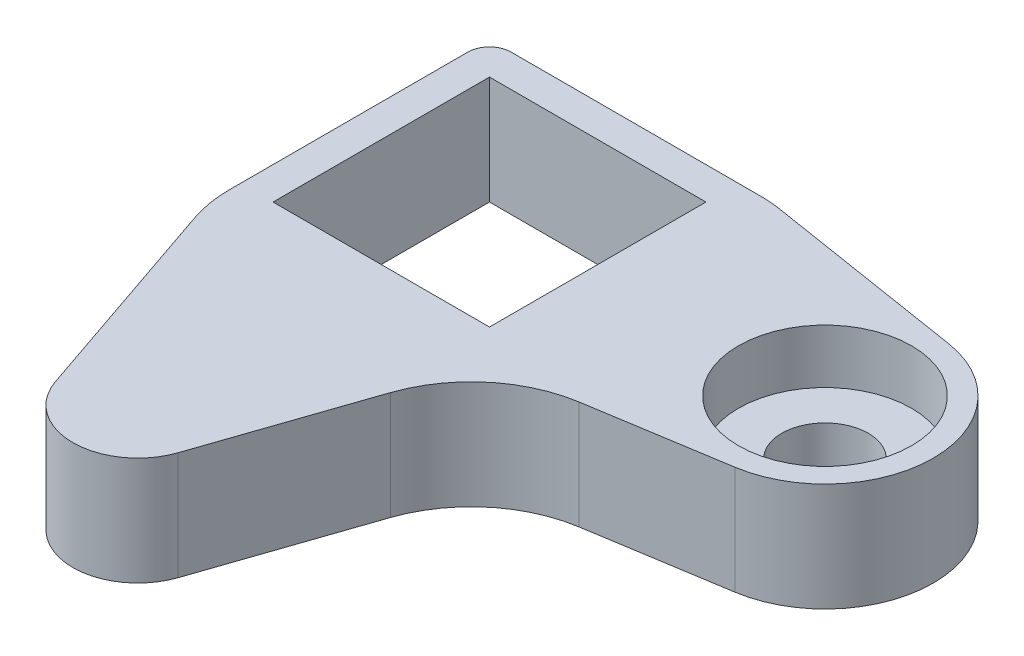
SolidWorks part; units mm, degrees
ref_plane "Front Plane" through (0, 0, 0) normal (0, 0, 1) x (1, 0, 0)
ref_plane "Top Plane" through (0, 0, 0) normal (0, 1, 0) x (1, 0, 0)
ref_plane "Right Plane" through (0, 0, 0) normal (1, 0, 0) x (0, 0, -1)
sketch "Sketch1" plane through (0, 0, 0) normal (0, 1, 0) x (1, 0, 0)
  line L0 (20, 0) -> (41, -10) construction
  line L1 (10, -42.5) -> (0, -20) construction
  line L2 (41, -10) -> (20, -20) construction
  line L3 (0, 0) -> (0, -20) construction
  line L4 (0, 0) -> (20, -20) construction
  line L5 (23.9399, 2.85) -> (42.5764, -0.125)
  line L12 (-3, -23) -> (23, -23) construction
  line L13 (0, 0) -> (20, 0) construction
  line L14 (0, 0) -> (0, -20) construction
  line L15 (0, -20) -> (20, -20) construction
  line L16 (20, 0) -> (20, -20) construction
  line L17 (10, -42.5) -> (20, -20) construction
  line L18 (-3, -21.0074) -> (-3, 1)
  line L19 (-1, 3) -> (22.0482, 3)
  line L20 (23, -23) -> (23, 3) construction
  line L21 (-3, -23) -> (23, 3) construction
  line L22 (-3, 3) -> (23, -23) construction
  line L23 (0, -20) -> (20, -20)
  line L24 (0, -20) -> (0, 0)
  line L25 (0, 0) -> (20, 0)
  line L26 (20, -20) -> (20, 0)
  line L27 (0, -20) -> (20, 0) construction
  line L28 (0, 0) -> (20, -20) construction
  line L29 (30.1306, -21.8617) -> (42.5764, -19.875)
  line L30 (20.6662, -29.8333) -> (15.678, -44.4392)
  line L31 (-2.356, -24.8857) -> (4.322, -44.4392)
  circle A4 centre (10, -42.5) radius 4 construction
  circle A5 centre (41, -10) radius 4 construction
  arc A6 (-3, 1) -> (-1, 3) centre (-1, 1) cw
  circle A7 centre (41, -10) radius 8 construction
  arc A8 (42.5764, -19.875) -> (42.5764, -0.125) centre (41, -10) ccw
  arc A9 (4.322, -44.4392) -> (15.678, -44.4392) centre (10, -42.5) ccw
  arc A10 (30.1306, -21.8617) -> (20.6662, -29.8333) centre (32.0222, -33.7117) ccw
  arc A11 (23.9399, 2.85) -> (22.0482, 3) centre (22.0482, -9) ccw
  arc A12 (-3, -21.0074) -> (-2.356, -24.8857) centre (9, -21.0074) ccw
  point P0 (10, -10)
  point P10 (10, -10)
  dimension "D6" = 8
  dimension "D7" = 16
  dimension "D8" = 20
  dimension "D9" = 12
  dimension "D10" = 12
  dimension "D11" = 12
  dimension "D5" = 2
  dimension "D2" = 20
  dimension "D3" = 3
  dimension "D4" = 42.5
  dimension "D12" = 20
  dimension "D13" = 41
extrude "Boss-Extrude1" add sketch "Sketch1" along normal blind 10
ref_plane "Plane1" through (0, 5, 0) normal (0, 1, 0) x (1, 0, 0)
sketch "Sketch2" plane through (0, 5, 0) normal (0, 1, 0) x (1, 0, 0)
  line L0 (20, 0) -> (41, -10) construction
  line L1 (10, -42.5) -> (0, -20) construction
  line L2 (41, -10) -> (20, -20) construction
  line L3 (0, 0) -> (0, -20) construction
  line L4 (0, 0) -> (20, -20) construction
  line L5 (23.9399, 2.85) -> (42.5764, -0.125) construction
  line L6 (-3, -23) -> (23, -23) construction
  line L7 (0, 0) -> (20, 0) construction
  line L8 (0, 0) -> (0, -20) construction
  line L9 (0, -20) -> (20, -20) construction
  line L10 (20, 0) -> (20, -20) construction
  line L11 (10, -42.5) -> (20, -20) construction
  line L12 (-3, -21.0074) -> (-3, 1) construction
  line L13 (-1, 3) -> (22.0482, 3) construction
  line L14 (23, -23) -> (23, 3) construction
  line L15 (-3, -23) -> (23, 3) construction
  line L16 (-3, 3) -> (23, -23) construction
  line L17 (0, -20) -> (20, -20) construction
  line L18 (0, -20) -> (0, 0) construction
  line L19 (0, 0) -> (20, 0) construction
  line L20 (20, -20) -> (20, 0) construction
  line L21 (0, -20) -> (20, 0) construction
  line L22 (0, 0) -> (20, -20) construction
  line L23 (30.1306, -21.8617) -> (42.5764, -19.875) construction
  line L24 (20.6662, -29.8333) -> (15.678, -44.4392) construction
  line L25 (-2.356, -24.8857) -> (4.322, -44.4392) construction
  circle A0 centre (10, -42.5) radius 4 construction
  circle A1 centre (41, -10) radius 4 construction
  arc A2 (-3, 1) -> (-1, 3) centre (-1, 1) cw construction
  circle A3 centre (41, -10) radius 8
  arc A4 (42.5764, -19.875) -> (42.5764, -0.125) centre (41, -10) ccw construction
  arc A5 (4.322, -44.4392) -> (15.678, -44.4392) centre (10, -42.5) ccw construction
  arc A6 (30.1306, -21.8617) -> (20.6662, -29.8333) centre (32.0222, -33.7117) ccw construction
  arc A7 (23.9399, 2.85) -> (22.0482, 3) centre (22.0482, -9) ccw construction
  arc A8 (-3, -21.0074) -> (-2.356, -24.8857) centre (9, -21.0074) ccw construction
  point P0 (10, -10)
  point P10 (10, -10)
  dimension "D2" = 8
  dimension "D7" = 2
  dimension "D8" = 16
  dimension "D9" = 20
  dimension "D10" = 12
  dimension "D11" = 12
  dimension "D12" = 12
  dimension "D1" = 20
  dimension "D3" = 20
  dimension "D4" = 41
  dimension "D5" = 42.5
  dimension "D6" = 3
extrude "Cut-Extrude2" cut sketch "Sketch2" along normal blind 46
sketch "Sketch3" plane through (0, 5, 0) normal (0, 1, 0) x (1, 0, 0)
  line L0 (20, 0) -> (41, -10) construction
  line L1 (10, -42.5) -> (0, -20) construction
  line L2 (41, -10) -> (20, -20) construction
  line L3 (0, 0) -> (0, -20) construction
  line L4 (0, 0) -> (20, -20) construction
  line L5 (23.9399, 2.85) -> (42.5764, -0.125) construction
  line L6 (-3, -23) -> (23, -23) construction
  line L7 (0, 0) -> (20, 0) construction
  line L8 (0, 0) -> (0, -20) construction
  line L9 (0, -20) -> (20, -20) construction
  line L10 (20, 0) -> (20, -20) construction
  line L11 (10, -42.5) -> (20, -20) construction
  line L12 (-3, -21.0074) -> (-3, 1) construction
  line L13 (-1, 3) -> (22.0482, 3) construction
  line L14 (23, -23) -> (23, 3) construction
  line L15 (-3, -23) -> (23, 3) construction
  line L16 (-3, 3) -> (23, -23) construction
  line L17 (0, -20) -> (20, -20) construction
  line L18 (0, -20) -> (0, 0) construction
  line L19 (0, 0) -> (20, 0) construction
  line L20 (20, -20) -> (20, 0) construction
  line L21 (0, -20) -> (20, 0) construction
  line L22 (0, 0) -> (20, -20) construction
  line L23 (30.1306, -21.8617) -> (42.5764, -19.875) construction
  line L24 (20.6662, -29.8333) -> (15.678, -44.4392) construction
  line L25 (-2.356, -24.8857) -> (4.322, -44.4392) construction
  circle A0 centre (10, -42.5) radius 4
  circle A1 centre (41, -10) radius 4
  arc A2 (-3, 1) -> (-1, 3) centre (-1, 1) cw construction
  circle A3 centre (41, -10) radius 8 construction
  arc A4 (42.5764, -19.875) -> (42.5764, -0.125) centre (41, -10) ccw construction
  arc A5 (4.322, -44.4392) -> (15.678, -44.4392) centre (10, -42.5) ccw construction
  arc A6 (30.1306, -21.8617) -> (20.6662, -29.8333) centre (32.0222, -33.7117) ccw construction
  arc A7 (23.9399, 2.85) -> (22.0482, 3) centre (22.0482, -9) ccw construction
  arc A8 (-3, -21.0074) -> (-2.356, -24.8857) centre (9, -21.0074) ccw construction
  point P0 (10, -10)
  point P10 (10, -10)
  dimension "D2" = 8
  dimension "D7" = 2
  dimension "D8" = 16
  dimension "D9" = 20
  dimension "D10" = 12
  dimension "D11" = 12
  dimension "D12" = 12
  dimension "D1" = 20
  dimension "D3" = 20
  dimension "D4" = 41
  dimension "D5" = 42.5
  dimension "D6" = 3
extrude "Cut-Extrude3" cut sketch "Sketch3" against normal blind 10
